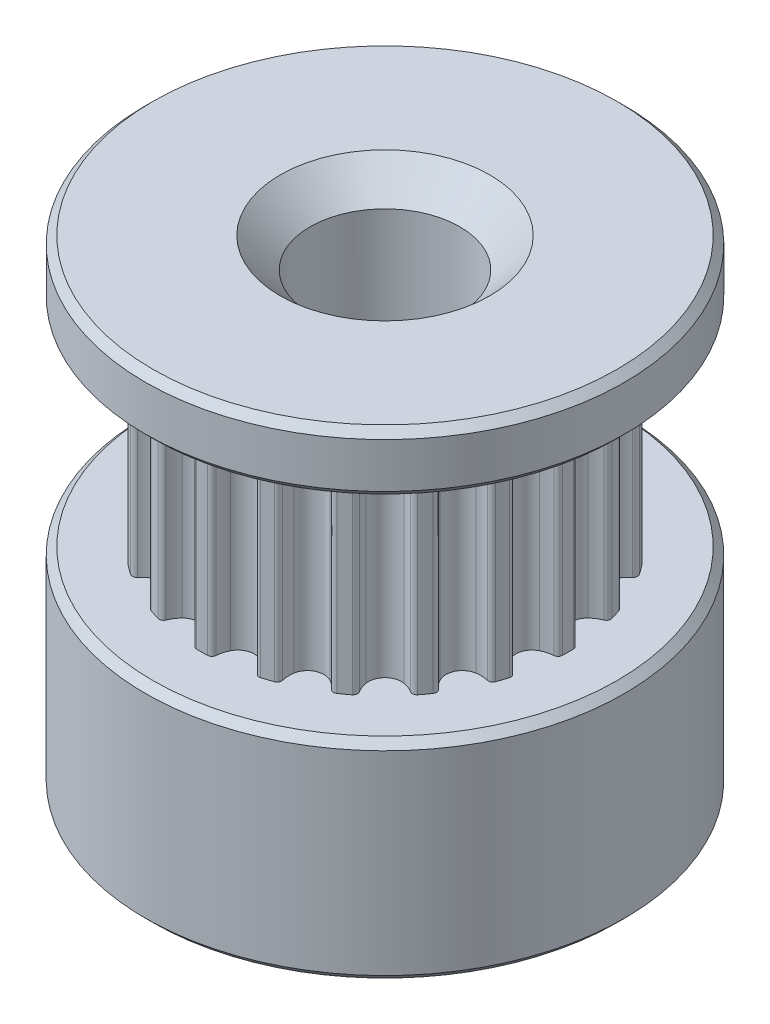
SolidWorks part; units mm, degrees
ref_plane "Front Plane" through (0, 0, 0) normal (0, 0, 1) x (1, 0, 0)
ref_plane "Top Plane" through (0, 0, 0) normal (0, 1, 0) x (1, 0, 0)
ref_plane "Right Plane" through (0, 0, 0) normal (1, 0, 0) x (0, 0, -1)
sketch "Sketch2" plane through (0, 0, 0) normal (0, 1, 0) x (1, 0, 0)
  circle A0 centre (0, 0) radius 6.3662
  dimension "D1" = 12.7324
extrude "Boss-Extrude1" add sketch "Sketch2" along normal blind 7
sketch "Sketch3" plane through (0, 7, 0) normal (0, 1, 0) x (1, 0, 0)
  line L0 (0, 0) -> (0, 6.1122) construction
  line L1 (0.9247, 5.8386) -> (0, 0) construction
  line L2 (0, 6.1122) -> (0, 6.7422)
  line L3 (1.3277, 6.039) -> (1.4477, 6.5849) construction
  line L4 (1.4477, 6.5849) -> (-4.4943, 7.8913) construction
  line L5 (0.6035, 6.1537) -> (0.658, 6.71) construction
  line L6 (1.8888, 5.813) -> (2.0835, 6.4122)
  arc A0 (0, 6.1122) -> (0.185, 6.1094) centre (0, 0) cw
  arc A1 (0.185, 6.1094) -> (0.3301, 5.9698) centre (0.1804, 5.9595) cw
  arc A2 (0.3301, 5.9698) -> (0.4323, 5.5937) centre (1.3277, 6.039) ccw
  arc A3 (0.4323, 5.5937) -> (1.3174, 5.4535) centre (0.9247, 5.8386) ccw
  arc A4 (0, 6.7422) -> (2.0835, 6.4122) centre (0, 0) cw
  arc A5 (0.658, 6.71) -> (1.4477, 6.5849) centre (0, 0) cw construction
  circle A6 centre (0, 0) radius 6.3662 construction
  arc A7 (1.5309, 5.7797) -> (1.3174, 5.4535) centre (0.6035, 6.1537) cw
  arc A8 (1.712, 5.8675) -> (1.5309, 5.7797) centre (1.67, 5.7235) ccw
  arc A9 (1.8888, 5.813) -> (1.712, 5.8675) centre (0, 0) ccw
  point P0 (1.0547, 6.6592)
  point P14 (0.8387, 5.2954)
  dimension "D1" = 0.15
  dimension "D2" = 1
  dimension "D3" = 0.55
  dimension "D5" = 0.63
  dimension "D7" = 0.254
  dimension "D8" = 9
  dimension "D6" = 1.3808
  dimension "D4" = 0.4
extrude "Cut-Extrude1" cut sketch "Sketch3" against normal blind 7
pattern_circular "CirPattern1" count 20 every 18 about axis through (0, 7, 0) along (0, -1, 0) of "Cut-Extrude1" reverse direction yes
sketch "Sketch4" plane through (0, 0, 0) normal (0, -1, 0) x (1, 0, 0)
  circle A0 centre (0, 0) radius 8
  dimension "D1" = 16
extrude "Boss-Extrude2" add sketch "Sketch4" along normal blind 7
extrude "Boss-Extrude3" add sketch "Sketch4<2>" against normal blind 2 from surface starting at face at (0, 7, 0)
sketch "Sketch4<2>" plane through (0, 0, 0) normal (0, -1, 0) x (1, 0, 0) same geometry as "Sketch4"
sketch "Sketch5" plane through (0, -7, 0) normal (0, -1, 0) x (1, 0, 0)
  circle A0 centre (0, 0) radius 2.5
  dimension "D1" = 5
extrude "Cut-Extrude2" cut sketch "Sketch5" against normal through all
chamfer "Chamfer1" distance 0.25 angle 45 4 edges at (0, -7, -8) (0, 0, -8) (0, 7, 8) (0, 9, 8)
chamfer "Chamfer2" distance 1 angle 45 1 edges at (0, 9, -2.5)
equation "\"teeth\"= 20"
equation "\"pitch\"= 2mm"
equation "\"diam\"= \"teeth\" * \"pitch\" / pi"
equation "\"D1@Sketch2\"=\"diam\""
equation "\"width\"= 7mm'Belt Width"
equation "\"D1@Boss-Extrude1\"=\"width\""
equation "\"D8@Sketch3\"=180/\"teeth\""
equation "\"D1@Cut-Extrude1\"=\"width\""
equation "\"D2@CirPattern1\"=360/\"teeth\""
equation "\"D1@CirPattern1\"=\"teeth\""
